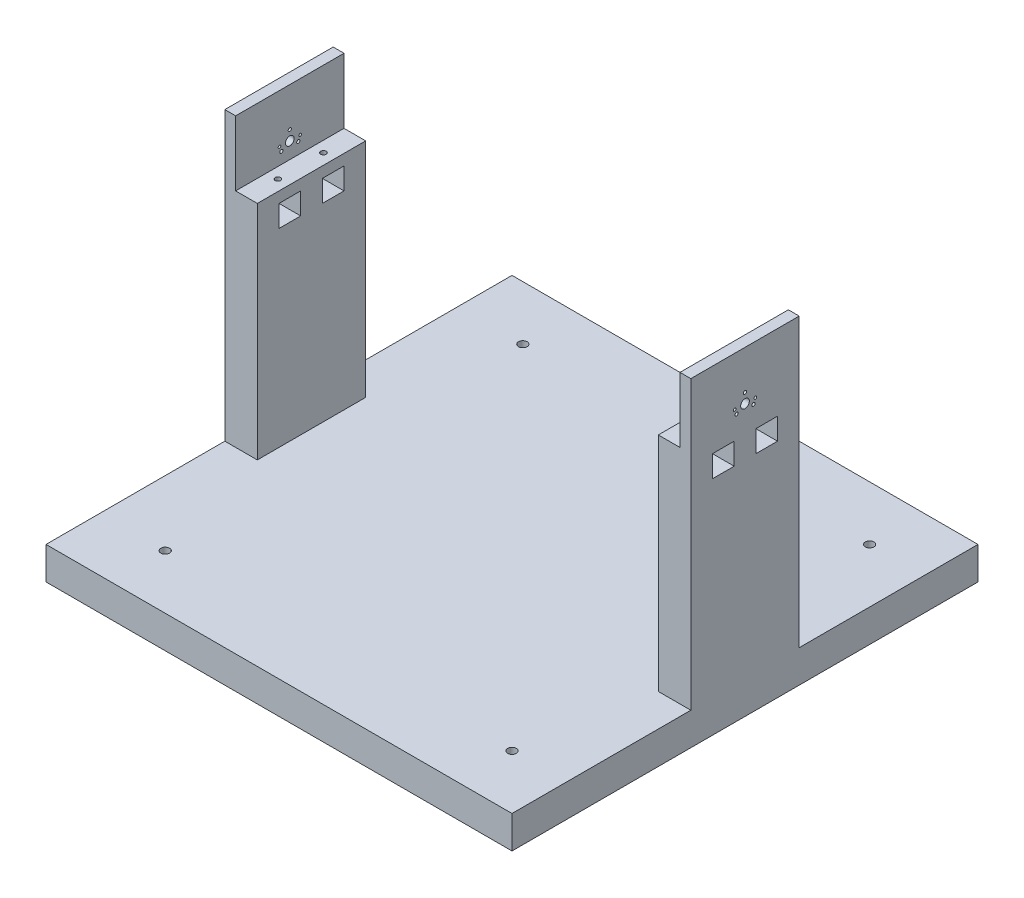
SolidWorks part; units mm, degrees
ref_plane "Plano frontal" through (0, 0, 0) normal (0, 0, 1) x (1, 0, 0)
ref_plane "Plano superior" through (0, 0, 0) normal (0, 1, 0) x (1, 0, 0)
ref_plane "Plano direito" through (0, 0, 0) normal (1, 0, 0) x (0, 0, -1)
sketch "Esboço1" plane through (0, 0, 0) normal (0, 1, 0) x (1, 0, 0)
  line L1 (0, 0) -> (430, 0)
  line L2 (0, 0) -> (0, 430)
  line L3 (0, 430) -> (430, 430)
  line L4 (430, 0) -> (430, 430)
  line L5 (0, 0) -> (20, 0)
  line L6 (0, 0) -> (0, 430)
  line L7 (0, 430) -> (20, 430)
  line L8 (20, 0) -> (20, 430)
  line L9 (430, 0) -> (410, 0)
  line L10 (430, 0) -> (430, 430)
  line L11 (430, 430) -> (410, 430)
  line L12 (410, 0) -> (410, 430)
  line L14 (0, 0) -> (0, 430)
  line L17 (0, 0) -> (-10, 0)
  line L18 (0, 0) -> (0, 430)
  line L19 (0, 430) -> (-10, 430)
  line L20 (-10, 0) -> (-10, 430)
extrude "Ressalto-extrusão1" add sketch "Esboço1" along normal blind 205 contours L1 L8 L3 L2 region at (10, 0, -215)
extrude "Ressalto-extrusão2" add sketch "Esboço1<3>" along normal blind 30 contours L1 L12 L3 L8 | L20 L17 L2 L19 region at (-5, 0, -215) region at (215, 0, -215)
sketch "Esboço1<3>" plane through (0, 0, 0) normal (0, 1, 0) x (1, 0, 0) same geometry as "Esboço1"
sketch "Esboço2" plane through (0, 205, 0) normal (0, 1, 0) x (1, 0, 0)
  line L1 (0, 430) -> (20, 430)
  line L2 (0, 430) -> (0, 0)
  line L3 (0, 0) -> (20, 0)
  line L4 (20, 430) -> (20, 0)
extrude "Ressalto-extrusão4" add sketch "Esboço2" along normal blind 30
sketch "Esboço4" plane through (0, 235, 0) normal (0, 1, 0) x (1, 0, 0)
  line L0 (20, 0) -> (20, 430) construction
  line L1 (20, 215) -> (0, 215)
  line L2 (20, 215) -> (20, 265)
  line L3 (20, 265) -> (0, 265)
  line L4 (0, 215) -> (0, 265)
  line L5 (0, 430) -> (0, 0) construction
  line L7 (20, 215) -> (0, 215)
  line L8 (20, 215) -> (20, 165)
  line L9 (20, 165) -> (0, 165)
  line L10 (0, 215) -> (0, 165)
  line M1 (0, 430) -> (0, 0)
  line M2 (0, 0) -> (20, 0)
  line M3 (20, 0) -> (20, 430)
  line M4 (20, 430) -> (0, 430)
extrude "Corte-extrusão1" cut sketch "Esboço4" against normal blind 205 contours L3 M3 M4 M1 | L9 M3 M1 M2 region at (10, 235, -347.5) region at (10, 235, -82.5)
sketch "Esboço6" plane through (0, 235, 0) normal (0, 1, 0) x (1, 0, 0)
  circle A0 centre (10, 236) radius 2.5
  circle A1 centre (10, 194) radius 2.5
extrude "Corte-extrusão3" cut sketch "Esboço6" against normal blind 10
ref_plane "Plano1" through (205, 0, 0) normal (1, 0, 0) x (0, 0, -1)
sketch "Esboço7" plane through (0, 235, 0) normal (0, 1, 0) x (1, 0, 0)
  line L0 (20, 165) -> (0, 165) construction
  line L1 (0, 265) -> (-10, 265)
  line L2 (0, 265) -> (0, 165)
  line L3 (0, 165) -> (-10, 165)
  line L4 (-10, 265) -> (-10, 165)
  line L5 (20, 165) -> (0, 165) construction
extrude "Ressalto-extrusão6" add sketch "Esboço7" against normal up to surface (235 mm away) and the other way blind 60 up to face at (200, 0, -215)
sketch "Esboço8" plane through (0, 0, 0) normal (1, 0, 0) x (0, 0, -1)
  circle A0 centre (215, 250) radius 4
  circle A1 centre (205.47, 250) radius 1.25
  circle A2 centre (224.53, 250) radius 1.25
  circle A3 centre (215, 259) radius 1.5
  circle A4 centre (207.2058, 245.5) radius 1.5
  circle A5 centre (222.7942, 245.5) radius 1.5
  point P14 (215, 250)
  dimension "D1" = 3
extrude "Corte-extrusão4" cut sketch "Esboço8" against normal up to next
sketch "Esboço9" plane through (-10, 0, 0) normal (-1, 0, 0) x (0, 0, 1)
  line L1 (-245, 225) -> (-225, 225)
  line L2 (-245, 225) -> (-245, 205)
  line L3 (-245, 205) -> (-225, 205)
  line L4 (-225, 225) -> (-225, 205)
  line L5 (-205, 225) -> (-185, 225)
  line L6 (-205, 225) -> (-205, 205)
  line L7 (-205, 205) -> (-185, 205)
  line L8 (-185, 225) -> (-185, 205)
extrude "Corte-extrusão5" cut sketch "Esboço9" against normal up to next
mirror "Espelhar1" about plane through (205, 0, 0) normal (1, 0, 0) of "Ressalto-extrusão1", "Ressalto-extrusão2", "Ressalto-extrusão4", "Corte-extrusão1", "Corte-extrusão3", "Ressalto-extrusão6", "Corte-extrusão4", "Corte-extrusão5"
sketch "Esboço10" plane through (0, 0, 0) normal (0, -1, 0) x (-1, 0, 0)
  circle A0 centre (-50, 380) radius 4
  circle A1 centre (-50, 50) radius 4
  circle A2 centre (-370, 380) radius 4
  circle A3 centre (-370, 50) radius 4
extrude "Corte-extrusão8" cut sketch "Esboço10" against normal up to next contours A0 | A1 | A3 | A2 region at (50, 0, -380) region at (50, 0, -50) region at (370, 0, -50)
